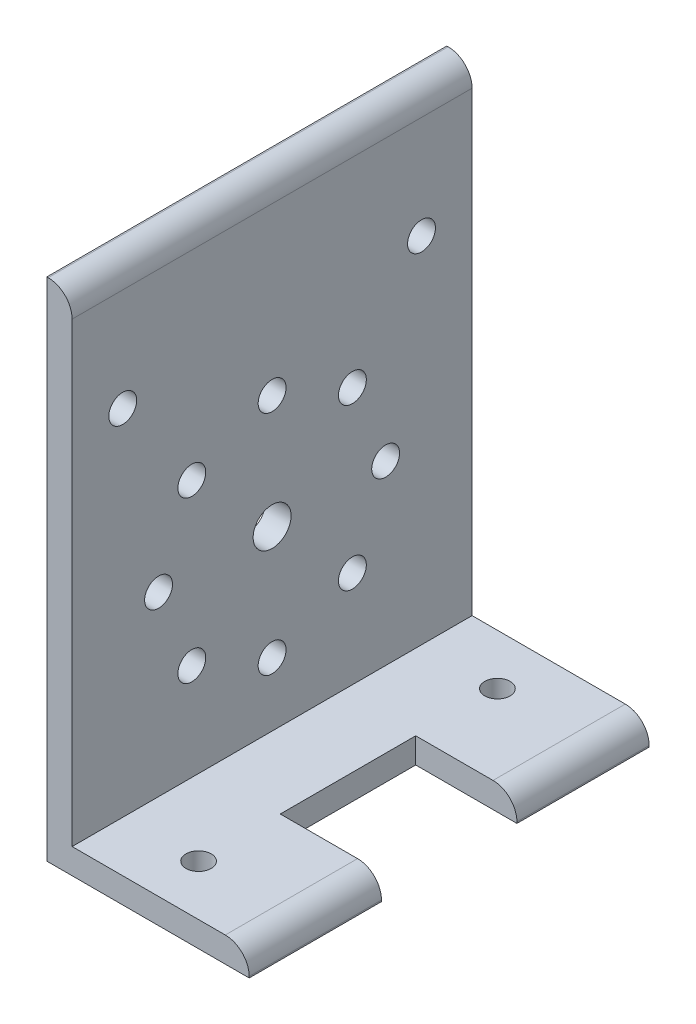
SolidWorks part; units mm, degrees
ref_plane "Front Plane" through (0, 0, 0) normal (0, 0, 1) x (1, 0, 0)
ref_plane "Top Plane" through (0, 0, 0) normal (0, 1, 0) x (1, 0, 0)
ref_plane "Right Plane" through (0, 0, 0) normal (1, 0, 0) x (0, 0, -1)
sketch "Sketch1" plane through (0, 0, 0) normal (0, 0, 1) x (1, 0, 0)
  line L0 (12.35, 6.35) -> (6.35, 6.35)
  line L1 (0, 0) -> (6.35, 0)
  line L2 (0, 0) -> (0, 127)
  line L3 (0, 127) -> (0.35, 127)
  line L4 (6.35, 37.75) -> (6.35, 121)
  line L5 (0, 0) -> (50.8, 0)
  line L6 (0, 0) -> (0, 6.35)
  line L7 (12.35, 6.35) -> (44.8, 6.35)
  line L8 (50.8, 0) -> (50.8, 0.35)
  line L9 (6.35, 6.35) -> (6.35, 37.75)
  arc A0 (44.8, 6.35) -> (50.8, 0.35) centre (44.8, 0.35) cw
  arc A1 (0.35, 127) -> (6.35, 121) centre (0.35, 121) cw
  point P10 (50.8, 6.35)
  point P13 (6.35, 127)
  dimension "D5" = 6
  dimension "D1" = 127
  dimension "D2" = 50.8
  dimension "D3" = 6.35
  dimension "D4" = 6.35
extrude "Boss-Extrude1" add sketch "Sketch1" along normal blind 100.4 contours L7 L4 A1 L3 L2 L1 L5 L8 A0 region at (28.575, 4.9822, 0)
sketch "Sketch2" plane through (0, 0, 0) normal (-1, 0, 0) x (0, 0, 1)
  line L0 (50.2, 0) -> (50.2, 127) construction
  line L1 (100.4, 0) -> (0, 0) construction
  line L2 (100.4, 127) -> (0, 127) construction
  line L3 (100.4, 50.8) -> (0, 50.8) construction
  line L4 (100.4, 0) -> (100.4, 127) construction
  line L5 (0, 0) -> (0, 127) construction
  circle A0 centre (50.2, 50.8) radius 28.5 construction
  circle A9 centre (50.2, 50.8) radius 4.7625
  circle A10 centre (50.2, 79.3) radius 3.5
  circle A18 centre (70.3525, 70.9525) radius 3.5
  circle A19 centre (78.7, 50.8) radius 3.5
  circle A20 centre (70.3525, 30.6475) radius 3.5
  circle A21 centre (50.2, 22.3) radius 3.5
  circle A22 centre (30.0475, 30.6475) radius 3.5
  circle A23 centre (21.7, 50.8) radius 3.5
  circle A24 centre (30.0475, 70.9525) radius 3.5
  dimension "D1" = 57
  dimension "D2" = 8
  dimension "D4" = 9.525
  dimension "D5" = 50.8
extrude "Cut-Extrude1" cut sketch "Sketch2" against normal through all
sketch "Sketch3" plane through (0, 6.35, 0) normal (0, 1, 0) x (1, 0, 0)
  line L0 (25.4, 0) -> (25.4, -100.4) construction
  line L1 (6.35, 0) -> (44.8, 0) construction
  line L2 (6.35, -100.4) -> (44.8, -100.4) construction
  line L3 (0, -100.4) -> (0, 0) construction
  circle A0 centre (25.4, -12.7) radius 3.175
  circle A2 centre (25.4, -87.7) radius 3.175
  dimension "D2" = 6.35
  dimension "D3" = 12.7
  dimension "D5" = 6.35
  dimension "D6" = 12.7
  dimension "D1" = 25.4
extrude "Cut-Extrude2" cut sketch "Sketch3" against normal through all
ref_plane "Width Centerline Plane" through (0, 0, 50.2) normal (0, 0, 1) x (1, 0, 0)
sketch "Sketch4" plane through (0, 6.35, 0) normal (0, 1, 0) x (1, 0, 0)
  line L0 (44.8, 0) -> (44.8, -100.4) construction
  line L5 (50.8, -100.4) -> (50.8, 0) construction
  line L6 (0, -50.2) -> (25.4, -50.2) construction
  line L9 (50.8, -50.2) -> (50.8, -33.2)
  line L10 (50.8, -33.2) -> (25.4, -33.2)
  line L11 (25.4, -50.2) -> (25.4, -33.2)
  line L13 (25.4, -50.2) -> (25.4, -67.2)
  line L14 (25.4, -67.2) -> (50.8, -67.2)
  line L15 (50.8, -50.2) -> (50.8, -67.2)
  point P8 (44.8, -50.2)
  dimension "D1" = 25.4
  dimension "D2" = 17
  dimension "D3" = 17
extrude "Cut-Extrude3" cut sketch "Sketch4" against normal through all
sketch "Sketch5" plane through (6.35, 0, 0) normal (1, 0, 0) x (0, 0, -1)
  line L0 (-50.2, 121) -> (-50.2, 6.35) construction
  line L1 (-100.4, 121) -> (0, 121) construction
  line L3 (-100.4, 6.35) -> (-100.4, 121) construction
  line L4 (-100.4, 6.35) -> (0, 6.35) construction
  circle A0 centre (-87.7, 95.25) radius 3.5
  circle A1 centre (-12.7, 95.25) radius 3.5
  point P4 (-50.2, 6.35)
  point P12 (-48.25, 6.35)
  point P13 (-48.25, 6.35)
  point P14 (-48.25, 6.35)
  point P15 (0, 0)
  dimension "D1" = 7
  dimension "D2" = 25.75
  dimension "D3" = 12.7
extrude "Cut-Extrude4" cut sketch "Sketch5" against normal blind 10
